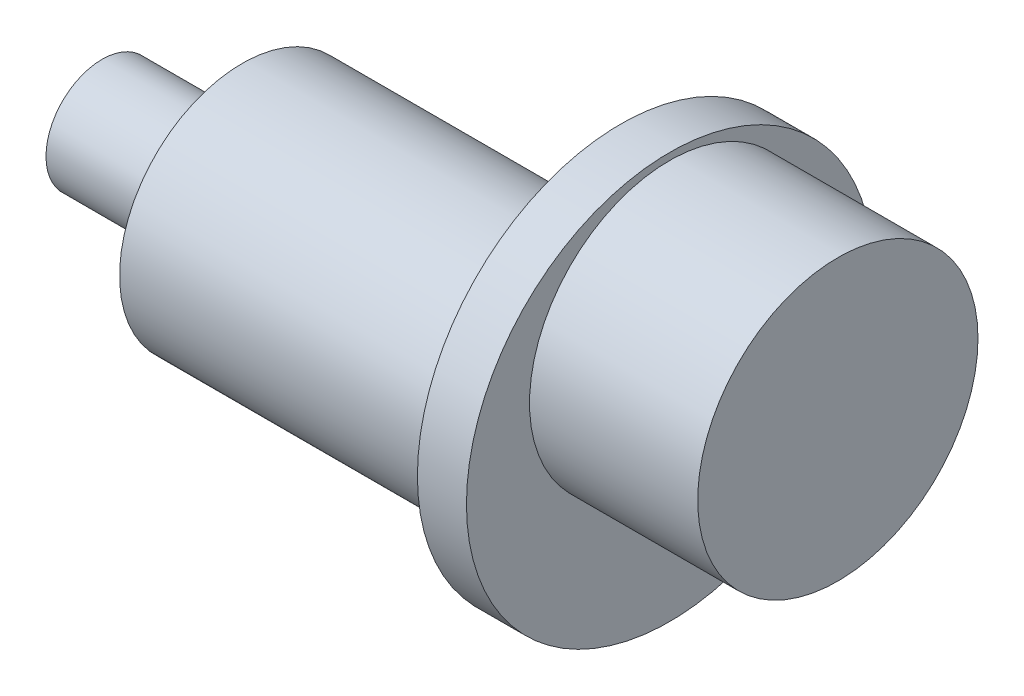
SolidWorks part; units mm, degrees
material "Acier non allié"
ref_plane "Plan de face" through (0, 0, 0) normal (0, 0, 1) x (1, 0, 0)
ref_plane "Plan de dessus" through (0, 0, 0) normal (0, 1, 0) x (1, 0, 0)
ref_plane "Plan de droite" through (0, 0, 0) normal (1, 0, 0) x (0, 0, -1)
sketch "Esquisse2" plane through (0, 0, 0) normal (1, 0, 0) x (0, 0, -1)
  circle A0 centre (0, 0) radius 17.5
  dimension "D1" = 35
extrude "Boss.-Extru.1" add sketch "Esquisse2" against normal blind 47
sketch "Esquisse3" plane through (-47, 0, 0) normal (-1, 0, 0) x (0, 0, 1)
  circle A0 centre (0, 0) radius 8
  dimension "D1" = 16
extrude "Boss.-Extru.2" add sketch "Esquisse3" along normal blind 20
sketch "Esquisse4" plane through (0, 0, 0) normal (1, 0, 0) x (0, 0, -1)
  circle A0 centre (0, 0) radius 20.5
  point P2 (0, 0)
  dimension "D1" = 41
extrude "Boss.-Extru.3" add sketch "Esquisse4" along normal blind 7
sketch "Esquisse5" plane through (7, 0, 0) normal (1, 0, 0) x (0, 0, -1)
  line L0 (0, 0) -> (0, 8) construction
  line L1 (-20.5, 0) -> (43.8068, 0) construction
  line L2 (0, -20.5) -> (0, 26.0972) construction
  circle A0 centre (0, 8) radius 29
  circle A1 centre (0, 0) radius 20.5 construction
  point P12 (0, 12.5608)
  point P13 (0, 8.7656)
  point P14 (0, 8.0065)
  dimension "D1" = 8
  dimension "D2" = 58
extrude "Boss.-Extru.4" add sketch "Esquisse5" along normal blind 7
sketch "Esquisse6" plane through (14, 0, 0) normal (1, 0, 0) x (0, 0, -1)
  line L0 (-29, 8) -> (40.7435, 8) construction
  line L1 (0, 8) -> (0, 40.9311) construction
  circle A0 centre (0, 16) radius 20
  circle A1 centre (0, 8) radius 29 construction
  point P10 (0, 0)
  point P11 (0, 16.8491)
  dimension "D1" = 40
  dimension "D2" = 8
extrude "Boss.-Extru.5" add sketch "Esquisse6" along normal blind 24
ref_point "Point1"
ref_axis "Axe1" through (-72.25, 0, 0) along (1, 0, 0)
ref_axis "Axe2" through (0, 39.9, 0) along (0, -1, 0)
ref_axis "Axe3" through (0, 0, -31.9) along (0, 0, 1)
